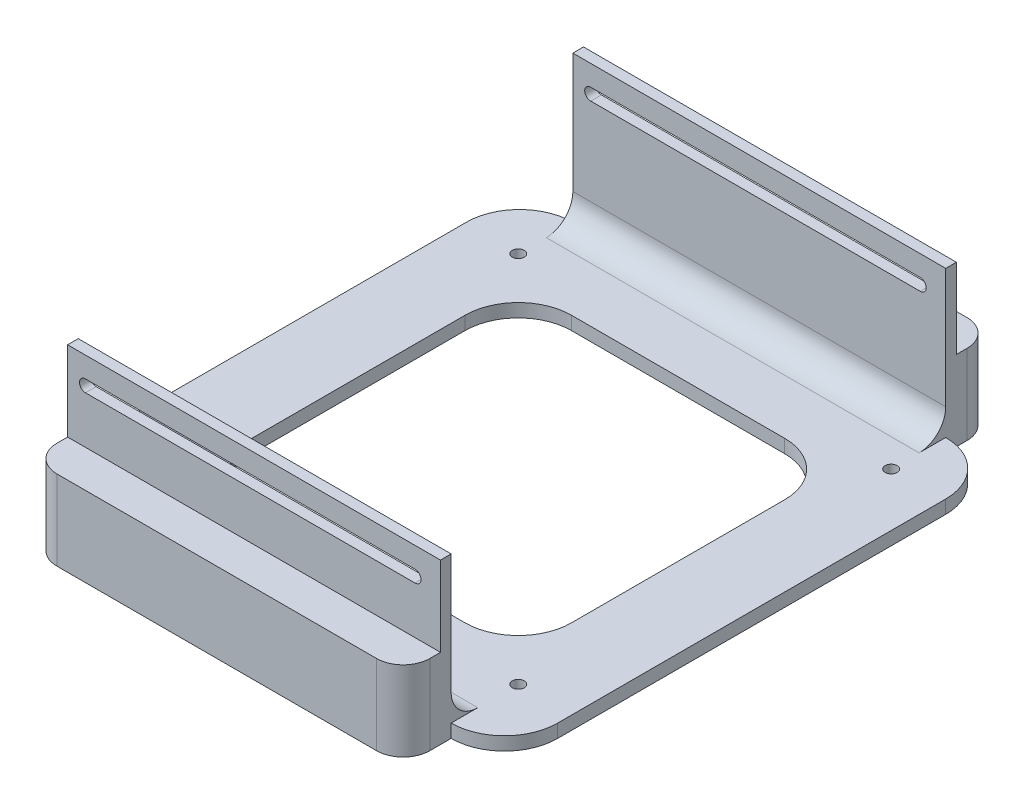
SolidWorks part; units mm, degrees
ref_plane "Front Plane" through (0, 0, 0) normal (0, 0, 1) x (1, 0, 0)
ref_plane "Top Plane" through (0, 0, 0) normal (0, 1, 0) x (1, 0, 0)
ref_plane "Right Plane" through (0, 0, 0) normal (1, 0, 0) x (0, 0, -1)
sketch "Sketch1" plane through (0, 0, 0) normal (0, 1, 0) x (1, 0, 0)
  line L0 (0, -99.5) -> (0, 99.5) construction
  line L1 (-70, -70) -> (70, -70) construction
  line L2 (-70, -70) -> (-70, 70) construction
  line L3 (-70, 70) -> (70, 70) construction
  line L4 (70, -70) -> (70, 70) construction
  line L5 (-70, -70) -> (70, 70) construction
  line L6 (-70, 70) -> (70, -70) construction
  line L7 (-70, 90.5) -> (70, 90.5)
  line L9 (90, -75.2) -> (90, 70.5)
  line L11 (-90, -75.2) -> (-90, 70.5)
  line L12 (40, -60) -> (-40, -60)
  line L13 (90, 90) -> (-90, -90) construction
  line L14 (60, -40) -> (60, 40)
  line L15 (40, 60) -> (-40, 60)
  line L16 (-60, -40) -> (-60, 40)
  line L17 (60, -60) -> (-60, 60) construction
  line L18 (60, 60) -> (-60, -60) construction
  line L20 (-70, 90.5) -> (-70, 98.5)
  line L21 (-60, 108.5) -> (60, 108.5)
  line L22 (70, 90.5) -> (70, 98.5)
  line L23 (-70, 90.5) -> (70, 108.5) construction
  line L24 (-70, 108.5) -> (70, 90.5) construction
  line L26 (-70, -95.2) -> (-70, -103.2)
  line L27 (-60, -113.2) -> (60, -113.2)
  line L28 (70, -95.2) -> (70, -103.2)
  line L29 (-70, -95.2) -> (70, -113.2) construction
  line L30 (-70, -113.2) -> (70, -95.2) construction
  line L31 (70, -95.2) -> (-70, -95.2)
  circle A0 centre (-70, 70) radius 2.25
  circle A1 centre (70, 70) radius 2.25
  circle A3 centre (-70, -70) radius 2.25
  arc A4 (-70, -95.2) -> (-90, -75.2) centre (-70, -75.2) cw
  arc A5 (90, 70.5) -> (70, 90.5) centre (70, 70.5) ccw
  arc A6 (-70, 90.5) -> (-90, 70.5) centre (-70, 70.5) ccw
  arc A7 (70, -95.2) -> (90, -75.2) centre (70, -75.2) ccw
  arc A8 (-40, -60) -> (-60, -40) centre (-40, -40) cw
  arc A9 (40, -60) -> (60, -40) centre (40, -40) ccw
  arc A10 (60, 40) -> (40, 60) centre (40, 40) ccw
  arc A11 (-40, 60) -> (-60, 40) centre (-40, 40) ccw
  arc A12 (60, 108.5) -> (70, 98.5) centre (60, 98.5) cw
  arc A13 (-70, 98.5) -> (-60, 108.5) centre (-60, 98.5) cw
  arc A14 (60, -113.2) -> (70, -103.2) centre (60, -103.2) ccw
  arc A15 (-70, -103.2) -> (-60, -113.2) centre (-60, -103.2) ccw
  circle A16 centre (70, -70) radius 2.25
  point P0 (0, 0)
  point P8 (0, 0)
  point P10 (0, 0)
  point P13 (0, 0)
  point P26 (-90, 90)
  point P27 (0, 0)
  point P48 (0, 99.5)
  point P51 (0, -104.2)
  dimension "D2" = 4.5
  dimension "D5" = 20
  dimension "D7" = 20
  dimension "D8" = 20
  dimension "D9" = 10
  dimension "D1" = 140
  dimension "D3" = 199
  dimension "D4" = 180
  dimension "D6" = 120
  dimension "D10" = 8
extrude "Boss-Extrude2" add sketch "Sketch1" along normal blind 5 contours L31 A7 L9 A5 L7 A6 L11 A4 A11 L15 A10 L14 A9 L12 A8 L16 A0 A1 A3 region at (0, 0, -87.9138)
extrude "Boss-Extrude3" add sketch "Sketch1<3>" along normal blind 30 contours L26 A15 L27 A14 L28 L31 | A13 L20 L7 L22 A12 L21 region at (0, 0, -99.3828) region at (0, 0, 104.0828)
sketch "Sketch1<3>" plane through (0, 0, 0) normal (0, 1, 0) x (1, 0, 0) same geometry as "Sketch1"
sketch "Sketch4" plane through (0, 30, 0) normal (0, 1, 0) x (1, 0, 0)
  line L0 (70, 90.5) -> (70, 98.5) construction
  line L1 (-70, 90.5) -> (70, 90.5)
  line L2 (-70, 90.5) -> (-70, 94.5)
  line L3 (-70, 94.5) -> (70, 94.5)
  line L4 (70, 90.5) -> (70, 94.5)
  line L5 (-70, 90.5) -> (70, 94.5) construction
  line L6 (-70, 94.5) -> (70, 90.5) construction
  line L7 (70, -95.2) -> (70, -103.2) construction
  line L8 (-70, -95.2) -> (70, -95.2)
  line L9 (-70, -95.2) -> (-70, -99.2)
  line L10 (-70, -99.2) -> (70, -99.2)
  line L11 (70, -95.2) -> (70, -99.2)
  line L12 (-70, -95.2) -> (70, -99.2) construction
  line L13 (-70, -99.2) -> (70, -95.2) construction
  point P4 (0, 92.5)
  point P12 (0, -97.2)
extrude "Boss-Extrude4" add sketch "Sketch4" along normal blind 30
sketch "Sketch5" plane through (0, 0, 99.2) normal (0, 0, 1) x (1, 0, 0)
  line L0 (-63.304, 50) -> (60.4383, 50) construction
  line L1 (-63.304, 52.25) -> (60.4383, 52.25)
  line L2 (-63.304, 47.75) -> (60.4383, 47.75)
  line L3 (-70, 30) -> (70, 30) construction
  arc A0 (-63.304, 52.25) -> (-63.304, 47.75) centre (-63.304, 50) ccw
  arc A1 (60.4383, 47.75) -> (60.4383, 52.25) centre (60.4383, 50) ccw
  point P2 (-1.4328, 50)
  dimension "D1" = 2.25
  dimension "D2" = 20
extrude "Cut-Extrude1" cut sketch "Sketch5" against normal up to surface (193.7 mm away) up to face at (0, 45, -94.5)
fillet "Fillet1" radius 10 2 edges at (0, 5, 95.2) (0, 5, -90.5)
